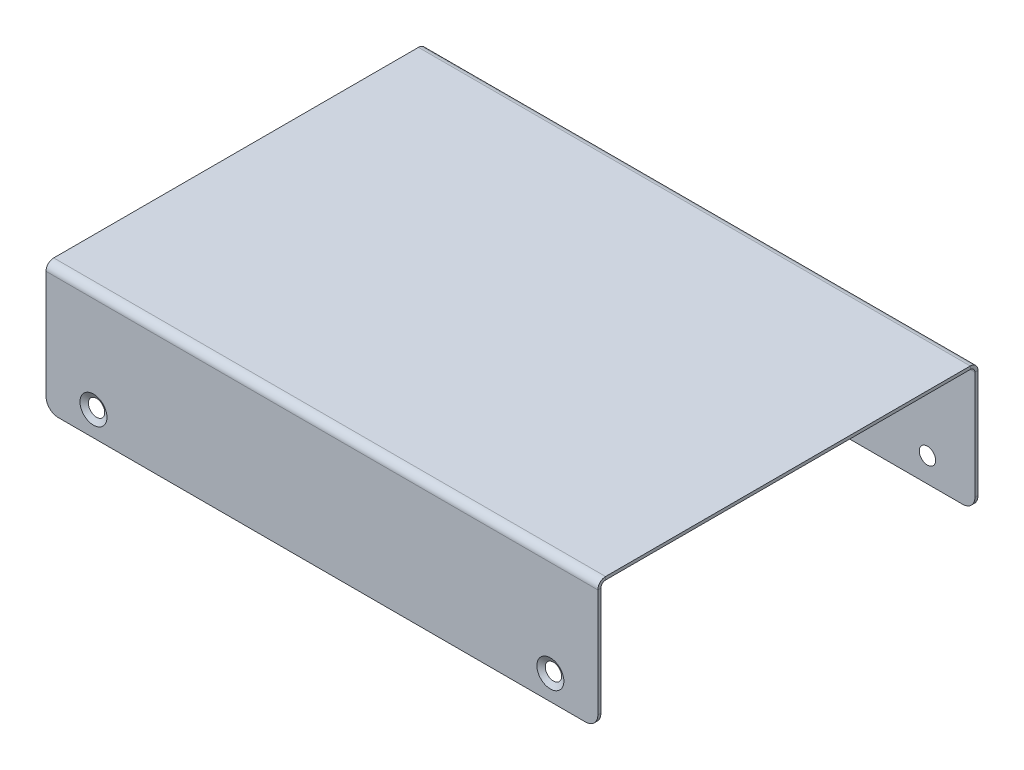
SolidWorks part; units mm, degrees
note: The reader was unsure of these and kept them because the rebuilt part matched: flange length of "Edge-Flange1".
ref_plane "Front Plane" through (0, 0, 0) normal (0, 0, 1) x (1, 0, 0)
ref_plane "Top Plane" through (0, 0, 0) normal (0, 1, 0) x (1, 0, 0)
ref_plane "Right Plane" through (0, 0, 0) normal (1, 0, 0) x (0, 0, -1)
sketch "Sketch1" plane through (0, 0, 0) normal (0, 1, 0) x (1, 0, 0)
  line L0 (0, 30.495) -> (0, -30.495) construction
  line L1 (-44.99, 30.495) -> (44.99, 30.495)
  line L2 (-44.99, 30.495) -> (-44.99, -30.495)
  line L3 (-44.99, -30.495) -> (44.99, -30.495)
  line L4 (44.99, 30.495) -> (44.99, -30.495)
  line L5 (-44.99, 0) -> (44.99, 0) construction
  dimension "D1" = 60.99
  dimension "D2" = 89.98
base flange "Base-Flange1" sketch "Sketch1" thickness 0.5 reverse thickness direction no parameters "D1"=0.7595
edge flange "Edge-Flange1" sketch "Sketch10" flange profiles "Sketch10", "Sketch11" flange angle 90 flange length 20.42 flange position material outside bend radius 0.7595 thickness 0.5 relief rectangular parameters "D6"=10, "D8"=0.4
sketch "Sketch10" plane through (0, -0.5, 30.495) normal (0, 0, 1) x (-1, 0, 0)
  line L0 (44.99, 0) -> (-44.99, 0) construction
  line L1 (44.99, 0) -> (-44.99, 0)
  line L2 (-44.99, 0) -> (-44.99, 20.42)
  line L3 (-44.99, 20.42) -> (44.99, 20.42)
  line L4 (44.99, 20.42) -> (44.99, 0)
sketch "Sketch11" plane through (0, -0.5, -30.495) normal (0, 0, -1) x (1, 0, 0)
  line L0 (44.99, 0) -> (-44.99, 0) construction
  line L1 (44.99, 0) -> (-44.99, 0)
  line L2 (-44.99, 0) -> (-44.99, 20.42)
  line L3 (-44.99, 20.42) -> (44.99, 20.42)
  line L4 (44.99, 20.42) -> (44.99, 0)
bend "EdgeBend1" bend radius 0.7595 bend angle 90 parameters "D5"=1
bend "EdgeBend2" bend radius 0.7595 bend angle 90 parameters "D5"=2
hole_wizard "CSK for M2 Flat Head Machine Screw1" positions "Sketch17" profile "Sketch14" countersink size "M2" standard "ANSI Metric" end condition up to next
sketch "Sketch17" plane through (0, 0, 30.995) normal (0, 0, 1) x (1, 0, 0)
  line L0 (0, 0) -> (0, -20.92) construction
  line L1 (-44.99, -20.92) -> (44.99, -20.92) construction
  line L3 (37.25, -16.92) -> (-37.25, -16.92) construction
  point P2 (-37.25, -16.92)
  point P6 (37.25, -16.92)
  point P26 (0, -16.92)
  dimension "D2" = 4
  dimension "D3" = 74.5
sketch "Sketch14" plane through (-37.25, -16.92, 30.995) normal (1, 0, 0) x (0, -1, 0)
  line L0 (0, 0) -> (0, 0.5)
  line L1 (0, 0.5) -> (1.2, 0.5)
  line L2 (1.2, 0.5) -> (1.2, 0.5774)
  line L3 (1.2, 0.5774) -> (2.2, 0)
  line L5 (2.2, 0) -> (0, 0)
  line L6 (-1.2, 0.5774) -> (-2.2, 0) construction
  line L11 (0, -6.35) -> (0, 107.95) construction
  dimension "Thru Hole Dia." = 2.4
  dimension "Thru Hole Depth" = 0.5
  dimension "Near C'Sink Dia." = 4.4
  dimension "Near C'Sink Angle" = 120
hole_wizard "CSK for M2 Flat Head Machine Screw2" positions "Sketch21" profile "Sketch20" countersink size "M2" standard "ANSI Metric" end condition up to next
sketch "Sketch21" plane through (0, 0, -30.995) normal (0, 0, -1) x (-1, 0, 0)
  point P3 (-37.25, -16.92)
  point P9 (37.25, -16.92)
sketch "Sketch20" plane through (37.25, -16.92, -30.995) normal (1, 0, 0) x (0, 1, 0)
  line L0 (0, 0) -> (0, 0.5)
  line L1 (0, 0.5) -> (1.2, 0.5)
  line L2 (1.2, 0.5) -> (1.2, 0.5774)
  line L3 (1.2, 0.5774) -> (2.2, 0)
  line L5 (2.2, 0) -> (0, 0)
  line L6 (-1.2, 0.5774) -> (-2.2, 0) construction
  line L11 (0, -6.35) -> (0, 107.95) construction
  dimension "Thru Hole Dia." = 2.4
  dimension "Thru Hole Depth" = 0.5
  dimension "Near C'Sink Dia." = 4.4
  dimension "Near C'Sink Angle" = 120
fillet "Fillet1" radius 2 4 edges at (44.99, -20.92, -30.745) (44.99, -20.92, 30.745) (-44.99, -20.92, -30.745) (-44.99, -20.92, 30.745)
sketch "Bend-Lines1" plane through (0, 0, 0) normal (0, 1, 0) x (1, 0, 0)
sketch "Bounding-Box1" plane through (0, 0, 0) normal (0, 1, 0) x (1, 0, 0)
sheet metal parameters "Sheet-Metal(1)" thickness 0.5 parameters "D1"=0.7595
flat pattern "Flat-Pattern(1)" [suppressed]
sketch "Bend-Lines2" plane through (0, 0, 0) normal (0, 1, 0) x (1, 0, 0)
sketch "Bounding-Box2" [suppressed] plane through (0, 0, 0) normal (0, 1, 0) x (1, 0, 0)
sheet metal parameters "Sheet-Metal(2)" thickness 0.5 parameters "D1"=0.7595
flat pattern "Flat-Pattern(1)" [suppressed]
sketch "Bend-Lines3" plane through (0, 0, 0) normal (0, 1, 0) x (1, 0, 0)
sketch "Bounding-Box3" [suppressed] plane through (0, 0, 0) normal (0, 1, 0) x (1, 0, 0)
bend of the flat pattern "Flatten-<EdgeBend1>1"
bend of the flat pattern "Flatten-<EdgeBend2>1"
sheet metal parameters "Sheet-Metal(3)" thickness 0.5 parameters "D1"=0.7595
flat pattern "Flat-Pattern(1)" [suppressed]
sketch "Bend-Lines4" plane through (0, 0, 0) normal (0, 1, 0) x (1, 0, 0)
sketch "Bounding-Box4" [suppressed] plane through (0, 0, 0) normal (0, 1, 0) x (1, 0, 0)
bend of the flat pattern "Flatten-<EdgeBend1>2"
bend of the flat pattern "Flatten-<EdgeBend2>2"
sheet metal parameters "Sheet-Metal(4)" thickness 0.5 parameters "D1"=0.7595
flat pattern "Flat-Pattern(1)" [suppressed]
sketch "Bend-Lines5" plane through (0, 0, 0) normal (0, 1, 0) x (1, 0, 0)
sketch "Bounding-Box5" [suppressed] plane through (0, 0, 0) normal (0, 1, 0) x (1, 0, 0)
bend of the flat pattern "Flatten-<EdgeBend1>3"
bend of the flat pattern "Flatten-<EdgeBend2>3"
